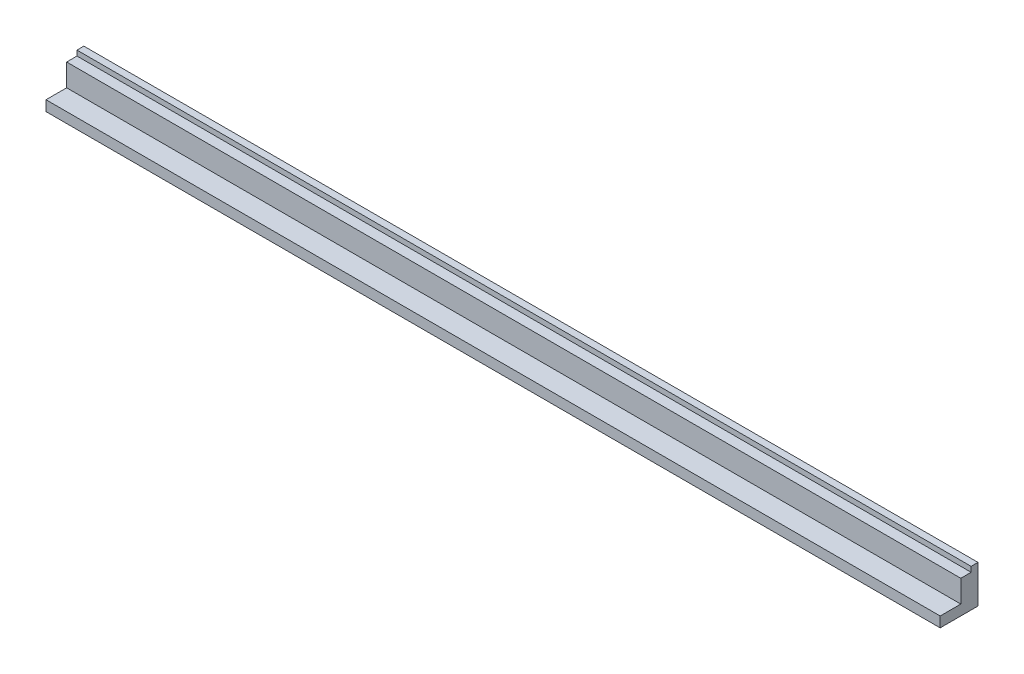
SolidWorks part; units mm, degrees
ref_plane "Спереди" through (0, 0, 0) normal (0, 0, 1) x (1, 0, 0)
ref_plane "Сверху" through (0, 0, 0) normal (0, 1, 0) x (1, 0, 0)
ref_plane "Справа" through (0, 0, 0) normal (1, 0, 0) x (0, 0, -1)
sketch "Эскиз1" plane through (0, 0, 0) normal (1, 0, 0) x (0, 0, -1)
  line L0 (0, 0) -> (-11, 0)
  line L1 (-11, 0) -> (-11, 3)
  line L2 (-11, 3) -> (-5, 3)
  line L3 (-5, 3) -> (-5, 9.5)
  line L4 (-5, 9.5) -> (-2, 9.5)
  line L5 (-2, 9.5) -> (-2, 11)
  line L6 (-2, 11) -> (0, 11)
  line L7 (0, 11) -> (0, 0)
  dimension "D1" = 5
  dimension "D2" = 11
  dimension "D3" = 3
  dimension "D4" = 6
  dimension "D5" = 6.5
  dimension "D6" = 11
  dimension "D7" = 1.5
  dimension "D8" = 2
extrude "Бобышка-Вытянуть1" add sketch "Эскиз1" along normal blind 260
